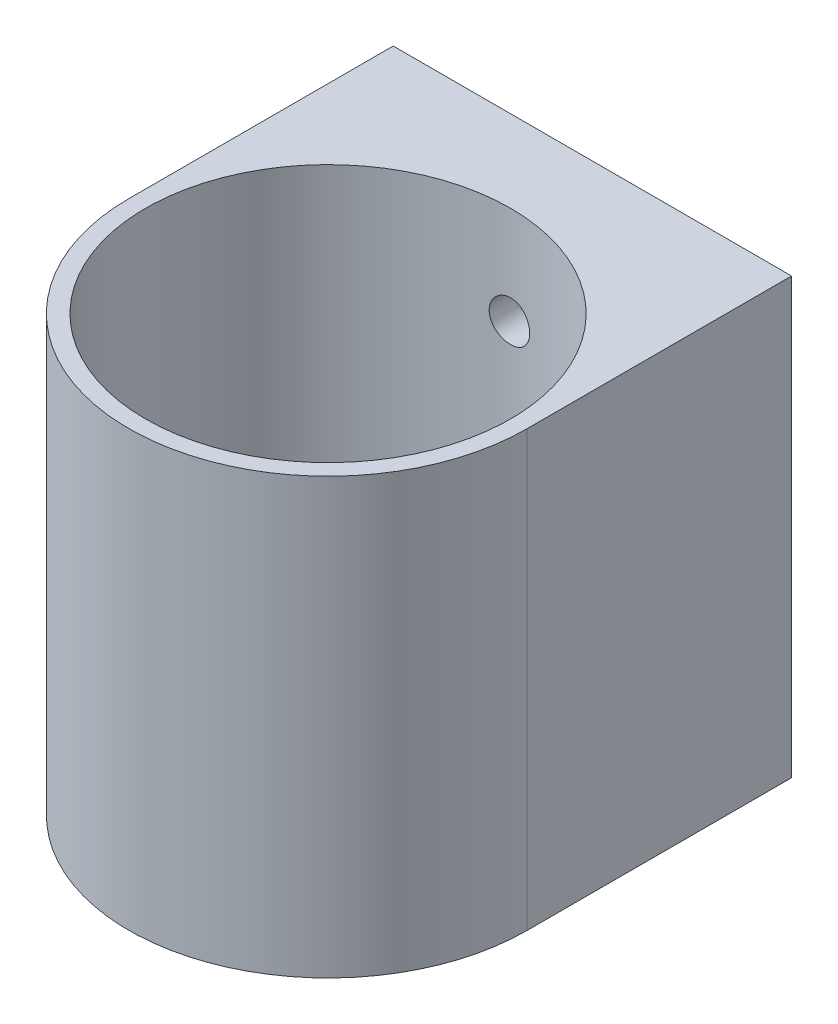
SolidWorks part; units mm, degrees
ref_plane "Front Plane" through (0, 0, 0) normal (0, 0, 1) x (1, 0, 0)
ref_plane "Top Plane" through (0, 0, 0) normal (0, 1, 0) x (1, 0, 0)
ref_plane "Right Plane" through (0, 0, 0) normal (1, 0, 0) x (0, 0, -1)
sketch "Sketch1" plane through (0, 0, 0) normal (0, 1, 0) x (1, 0, 0)
  line L1 (-45.5066, 16.4638) -> (9.4934, 16.4638)
  line L2 (-45.5066, 16.4638) -> (-45.5066, -16.0362)
  line L3 (-45.5066, -16.0362) -> (9.4934, -16.0362)
  line L4 (9.4934, 16.4638) -> (9.4934, -16.0362)
  circle A0 centre (-18.0066, -16.0362) radius 27.5
  circle A1 centre (-18.0066, -16.0362) radius 25.2
  dimension "D1" = 32.5
  dimension "D2" = 55
extrude "Boss-Extrude2" add sketch "Sketch1" along normal blind 60 contours A0 L4 L1 L2 | L3 A1 | L3 A1 | A0 region at (-18.0066, 0, -15.825) region at (-18.0066, 0, 5.341) region at (-18.0066, 0, 26.7314)
sketch "Sketch3" plane through (0, 0, 0) normal (0, -1, 0) x (-1, 0, 0)
  circle A0 centre (18.0066, -16.0362) radius 25.2
extrude "Boss-Extrude3" add sketch "Sketch3" against normal blind 9.3
sketch "Sketch4" plane through (0, 9.3, 0) normal (0, 1, 0) x (1, 0, 0)
  line L0 (-18.0066, -41.2362) -> (-18.0066, 9.1638)
  line L1 (-43.2066, -16.0362) -> (7.1934, -16.0362)
  circle A0 centre (-18.0066, -16.0362) radius 25.2 construction
  circle A1 centre (-18.0066, -16.0362) radius 25.2 construction
  circle A2 centre (-18.0066, -16.0362) radius 1.75
  circle A3 centre (-8.0066, -16.0362) radius 1.75
  circle A4 centre (1.9934, -16.0362) radius 1.75
  circle A5 centre (-18.0066, -6.0362) radius 1.75
  circle A6 centre (-18.0066, 3.9638) radius 1.75
  circle A7 centre (-28.0066, -16.0362) radius 1.75
  circle A8 centre (-38.0066, -16.0362) radius 1.75
  circle A9 centre (-18.0066, -26.0362) radius 1.75
  circle A10 centre (-18.0066, -36.0362) radius 1.75
  circle A11 centre (-28.0066, -6.0362) radius 1.75
  circle A12 centre (-8.0066, -6.0362) radius 1.75
  circle A13 centre (-8.0066, -26.0362) radius 1.75
  circle A14 centre (-28.0066, -26.0362) radius 1.75
  circle A15 centre (-18.0066, -1.0362) radius 1.75
  circle A16 centre (-23.0066, -6.0362) radius 1.75
  circle A17 centre (-13.0066, -6.0362) radius 1.75
  circle A18 centre (-18.0066, -11.0362) radius 1.75
  circle A19 centre (-18.0066, -21.0362) radius 1.75
  circle A20 centre (-18.0066, -31.0362) radius 1.75
  circle A21 centre (-23.0066, -16.0362) radius 1.75
  circle A22 centre (-33.0433, -16.0362) radius 1.75
  circle A23 centre (-13.0066, -16.0362) radius 1.75
  circle A24 centre (-3.1187, -16.0362) radius 1.75
  circle A25 centre (-13.0066, -21.0362) radius 1.75
  circle A26 centre (-23.0066, -21.0362) radius 1.75
  circle A27 centre (-28.0066, -21.0362) radius 1.75
  circle A28 centre (-33.0066, -21.0362) radius 1.75
  circle A29 centre (-23.0066, -26.0362) radius 1.75
  circle A30 centre (-13.0066, -26.0362) radius 1.75
  circle A31 centre (-13.0066, -31.0362) radius 1.75
  circle A32 centre (-23.0066, -31.0362) radius 1.75
  circle A33 centre (-8.0066, -21.0362) radius 1.75
  circle A34 centre (-3.0066, -21.0362) radius 1.75
  circle A35 centre (-23.0066, -11.0362) radius 1.75
  circle A36 centre (-28.0066, -11.0362) radius 1.75
  circle A37 centre (-33.0066, -11.0362) radius 1.75
  circle A38 centre (-13.0066, -11.0362) radius 1.75
  circle A39 centre (-8.0066, -11.0362) radius 1.75
  circle A40 centre (-3.0066, -11.0362) radius 1.75
  circle A41 centre (-23.0066, -1.0362) radius 1.75
  circle A42 centre (-13.0066, -1.0362) radius 1.75
  dimension "D1" = 10
  dimension "D2" = 10
  dimension "D3" = 10
  dimension "D4" = 10
  dimension "D9" = 5
  dimension "D15" = 5
  dimension "D5" = 10
  dimension "D6" = 10
  dimension "D7" = 10
  dimension "D8" = 10
  dimension "D10" = 5
  dimension "D11" = 5
  dimension "D12" = 5
  dimension "D13" = 5
  dimension "D14" = 5
  dimension "D16" = 5
  dimension "D17" = 5
  dimension "D18" = 5
  dimension "D19" = 5
  dimension "D20" = 5
  dimension "D21" = 5
  dimension "D22" = 5
  dimension "D23" = 5
  dimension "D24" = 5
extrude "Cut-Extrude1" cut sketch "Sketch4" against normal through all contours L0 A6 | L0 A6 | L0 A5 | L0 A5 | A11 | A12 | L1 A3 | L1 A3 | L1 A4 | L1 A4 | L0 A2 L1 | L0 A2 L1 | L1 A2 L0 | L1 A2 L0 | L1 A8 | L1 A8 | A14 | L0 A9 | L0 A9 | A13 | L0 A10 | L0 A10 | L1 A7 | L1 A7 | A7 | A37 | A36 | A35 | A16 | A41 | A15 | A42 | A17 | A38 | A39 | A40 | A24 | A34 | A33 | A25 | A23 | A18 | A21 | A22 | A28 | A27 | A26 | A19 | A31 | A20 | A32 | A29 | A30 region at (-18.7493, 9.3, 36.0362) region at (-38.0066, 9.3, 16.7789) region at (-38.0066, 9.3, 15.2935) region at (-28.0066, 9.3, 16.7789) region at (-28.0066, 9.3, 15.2935) region at (-18.7493, 9.3, -3.9638) region at (-17.2639, 9.3, -3.9638) region at (-18.7493, 9.3, 6.0362) region at (-17.2639, 9.3, 6.0362) region at (1.9934, 9.3, 15.2935) region at (1.9934, 9.3, 16.7789) region at (-8.0066, 9.3, 15.2935) region at (-8.0066, 9.3, 16.7789) region at (-18.7493, 9.3, 16.7789) region at (-17.2639, 9.3, 16.7789) region at (-18.7493, 9.3, 26.0362) region at (-17.2639, 9.3, 26.0362) region at (-17.2639, 9.3, 36.0362) region at (-18.7493, 9.3, 15.2935) region at (-17.2639, 9.3, 15.2935) region at (-28.0066, 9.3, 6.0362) region at (-8.0066, 9.3, 6.0362) region at (-8.0066, 9.3, 26.0362) region at (-28.0066, 9.3, 26.0362)
sketch "Sketch5" plane through (0, 0, -16.4638) normal (0, 0, -1) x (-1, 0, 0)
  line L1 (-9.4934, 60) -> (45.5066, 60)
  line L2 (-9.4934, 60) -> (-9.4934, 0)
  line L3 (-9.4934, 0) -> (45.5066, 0)
  line L4 (45.5066, 60) -> (45.5066, 0)
  circle A0 centre (18.0066, 46.5) radius 2.8
  circle A1 centre (18.0066, 13.5) radius 2.8
  point P10 (0, 0)
  dimension "D1" = 5.6
  dimension "D2" = 27.5
  dimension "D3" = 13.5
  dimension "D4" = 13.5
extrude "height increase" add sketch "Sketch5" along normal blind 4
extrude "Cut-Extrude2" cut sketch "Sketch5<2>" against normal blind 30 contours A0 | A1 region at (-18.0066, 46.5, -16.4638) region at (-18.0066, 13.5, -16.4638)
sketch "Sketch5<2>" plane through (0, 0, -16.4638) normal (0, 0, -1) x (-1, 0, 0) same geometry as "Sketch5"
